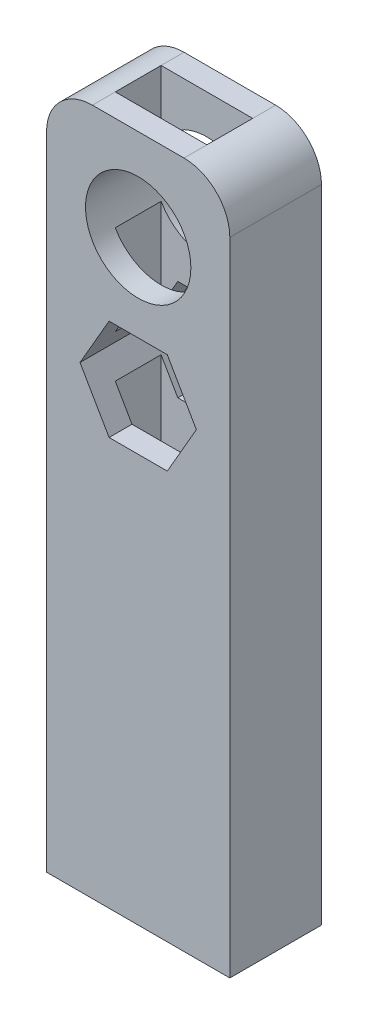
SolidWorks part; units mm, degrees
ref_plane "Plan de face" through (0, 0, 0) normal (0, 0, 1) x (1, 0, 0)
ref_plane "Plan de dessus" through (0, 0, 0) normal (0, 1, 0) x (1, 0, 0)
ref_plane "Plan de droite" through (0, 0, 0) normal (1, 0, 0) x (0, 0, -1)
sketch "Esquisse1" plane through (0, 0, 0) normal (0, 1, 0) x (1, 0, 0)
  line L1 (-40, 20) -> (0, 20)
  line L2 (-40, 20) -> (-40, 0)
  line L3 (-40, 0) -> (0, 0)
  line L4 (0, 20) -> (0, 0)
  dimension "D1" = 40
  dimension "D2" = 20
extrude "Boss.-Extru.2" add sketch "Esquisse1" along normal blind 150 contours L1 L4 L3 L2
sketch "Esquisse2" plane through (0, 0, 0) normal (0, 0, 1) x (1, 0, 0)
  line L0 (-40, 150) -> (-40, 0) construction
  line L1 (0, 150) -> (0, 0) construction
  line L2 (-40, 150) -> (0, 150) construction
  circle A0 centre (-20, 130) radius 11.5
  dimension "D1" = 40
  dimension "D2" = 20
  dimension "D3" = 20
  dimension "D4" = 23
extrude "Enlèv. mat.-Extru.1" cut sketch "Esquisse2" against normal through all contours A0
sketch "Esquisse3" plane through (0, 0, 0) normal (0, 0, 1) x (1, 0, 0)
  line L0 (0, 150) -> (0, 0) construction
  line L1 (-26.3509, 111) -> (-32.7017, 100)
  line L2 (-32.7017, 100) -> (-26.3509, 89)
  line L3 (-26.3509, 89) -> (-13.6491, 89)
  line L4 (-13.6491, 89) -> (-7.2983, 100)
  line L5 (-7.2983, 100) -> (-13.6491, 111)
  line L6 (-13.6491, 111) -> (-26.3509, 111)
  line L8 (-40, 150) -> (0, 150) construction
  circle A0 centre (-20, 100) radius 11 construction
  dimension "D4" = 22
  dimension "D1" = 20
  dimension "D2" = 50
  dimension "D3" = 0
extrude "Enlèv. mat.-Extru.2" cut sketch "Esquisse3" against normal through all
sketch "Esquisse4" plane through (0, 150, 0) normal (0, 1, 0) x (1, 0, 0)
  line L0 (0, 20) -> (0, 0) construction
  line L1 (-30, 5) -> (-10, 5)
  line L2 (-30, 5) -> (-30, 15)
  line L3 (-30, 15) -> (-10, 15)
  line L4 (-10, 5) -> (-10, 15)
  line L5 (-40, 20) -> (-40, 0) construction
  line L6 (-40, 20) -> (0, 20) construction
  line L7 (-40, 0) -> (0, 0) construction
  dimension "D1" = 10
  dimension "D2" = 10
  dimension "D3" = 5
  dimension "D4" = 5
extrude "Enlèv. mat.-Extru.3" cut sketch "Esquisse4" against normal through all both and the other way through all
fillet "Congé2" radius 10 1 edges at (0, 150, -10)
fillet "Congé5" radius 10 1 edges at (-40, 150, -10)
